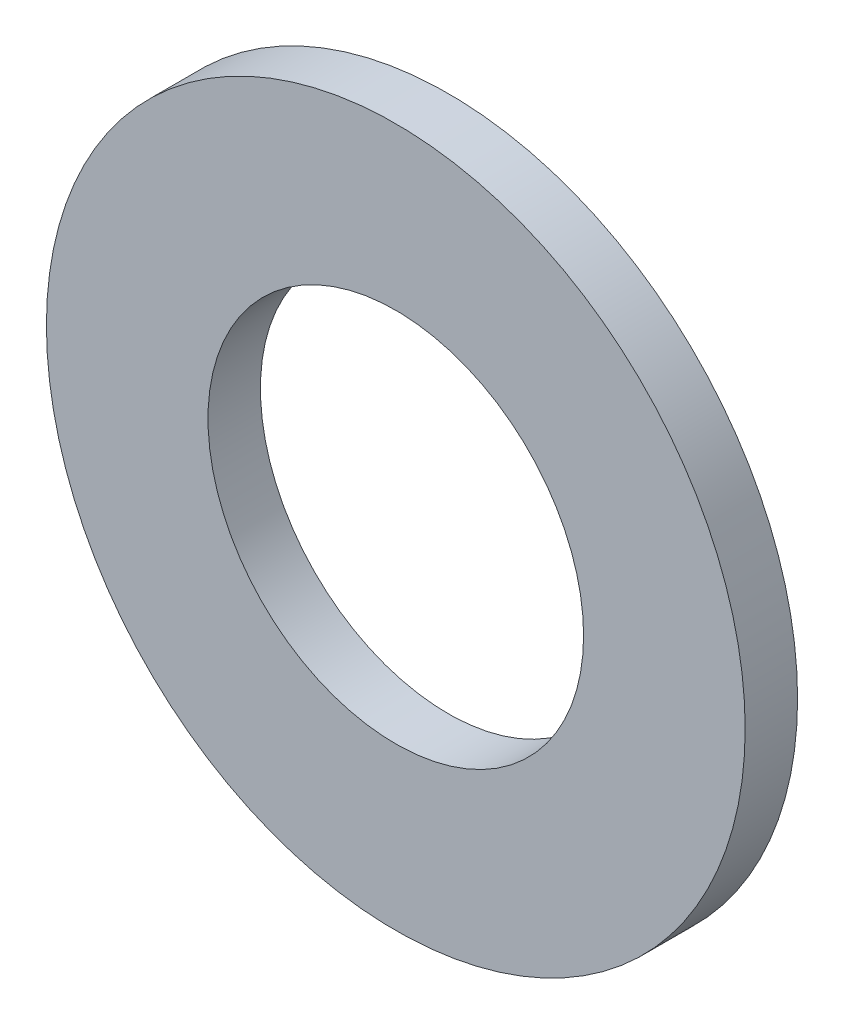
SolidWorks part; units mm, degrees
material "Alloy Steel"
ref_plane "Front Plane" through (0, 0, 0) normal (0, 0, 1) x (1, 0, 0)
ref_plane "Top Plane" through (0, 0, 0) normal (0, 1, 0) x (1, 0, 0)
ref_plane "Right Plane" through (0, 0, 0) normal (1, 0, 0) x (0, 0, -1)
sketch "Sketch1" plane through (0, 0, 0) normal (0, 0, 1) x (1, 0, 0)
  circle A0 centre (0, 0) radius 4
  circle A1 centre (0, 0) radius 2.15
  dimension "OD" = 8
  dimension "ID1" = 4.3
extrude "Boss-Extrude1" add sketch "Sketch1" along normal blind 0.6
ref_axis "Center Axis 1" [suppressed] through (0, 0, 0.6) along (0, 0, -1)
ref_plane "Contact Plane 1" [suppressed] through (0, 0, 0.6) normal (0, 0, 1) x (1, 0, 0)
ref_plane "Contact Plane 2" [suppressed] through (0, 0, 0) normal (0, 0, -1) x (-1, 0, 0)
